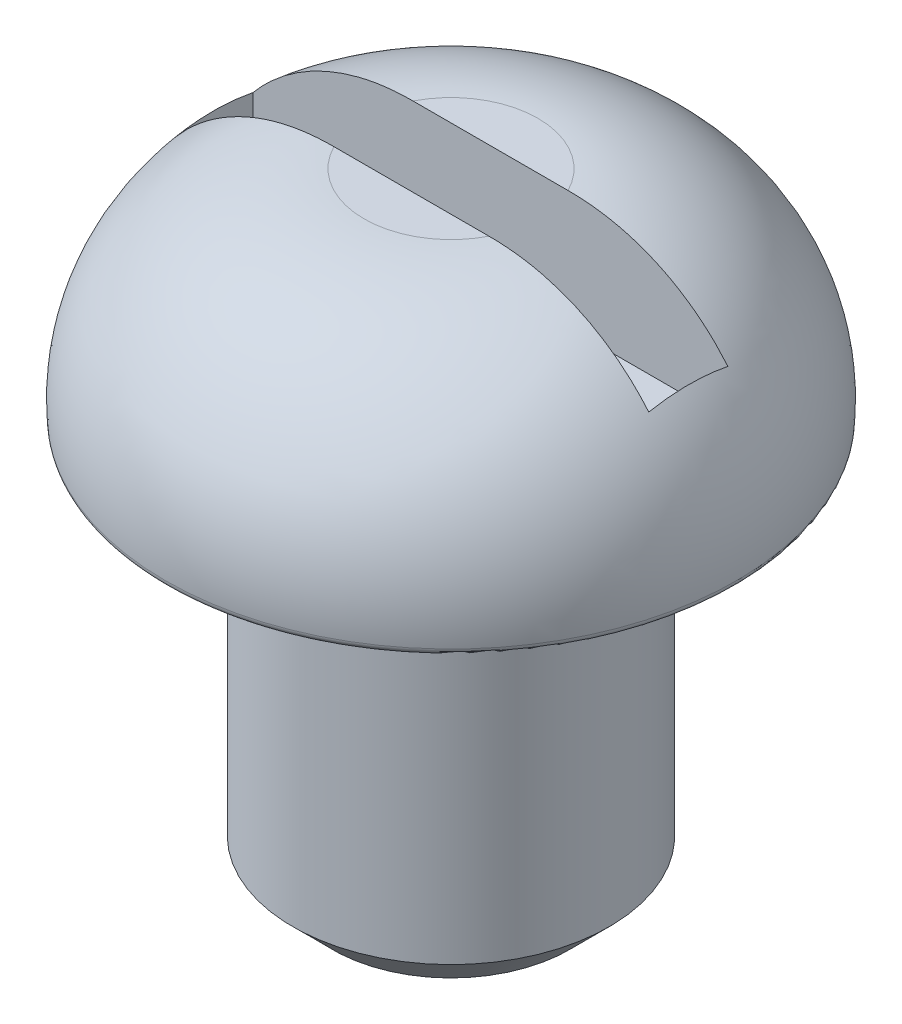
SolidWorks part; units mm, degrees
ref_plane "Спереди" through (0, 0, 0) normal (0, 0, 1) x (1, 0, 0)
ref_plane "Сверху" through (0, 0, 0) normal (0, 1, 0) x (1, 0, 0)
ref_plane "Справа" through (0, 0, 0) normal (1, 0, 0) x (0, 0, -1)
sketch "Эскиз1" plane through (0, 0, 0) normal (0, 0, 1) x (1, 0, 0)
  line L0 (3.6, 5) -> (2, 5)
  line L1 (0, 0) -> (0, 7.8)
  line L2 (2, 5) -> (2, 0.5)
  line L3 (2, 0.5) -> (1.5, 0)
  line L4 (1.5, 0) -> (0, 0)
  line L5 (0, 7.8) -> (1.1, 7.8)
  arc A0 (1.1, 7.8) -> (3.6, 5) centre (1.1, 5.2839) cw
  dimension "D2" = 1.1
  dimension "D1" = 5
  dimension "D3" = 2
  dimension "D4" = 1.5
  dimension "D5" = 2.8
  dimension "D6" = 3.6
  dimension "D7" = 45
revolve "Повернуть1" add sketch "Эскиз1" angle 360 about L1
fillet "Скругление1" radius 0.1 1 edges at (0, 5, -3.6)
sketch "Эскиз3" plane through (0, 7.8, 0) normal (0, 1, 0) x (-1, 0, 0)
  line L1 (3, -0.5) -> (-3, -0.5)
  line L2 (3, -0.5) -> (3, 0.5)
  line L3 (3, 0.5) -> (-3, 0.5)
  line L4 (-3, -0.5) -> (-3, 0.5)
  dimension "D1" = 1
  dimension "D2" = 0.5
  dimension "D3" = 6
  dimension "D4" = 3
extrude "Вырез-Вытянуть2" cut sketch "Эскиз3" against normal blind 1.5
ref_axis "Ось1" through (0, -104.1565, 0) along (0, 1, 0)
